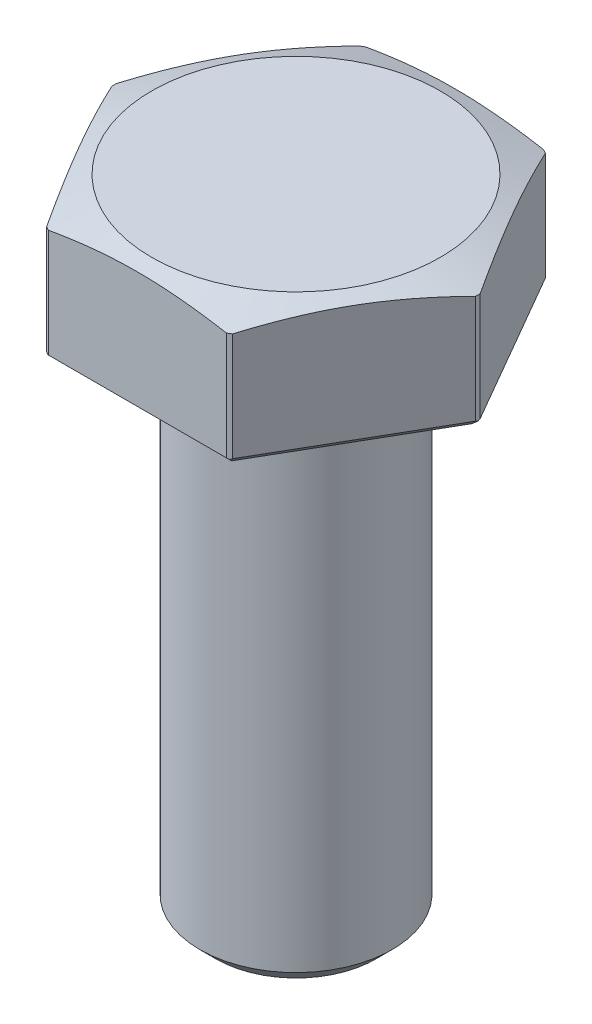
SolidWorks part; units mm, degrees
material "Chrome Stainless Steel"
ref_plane "Front" through (0, 0, 0) normal (0, 0, 1) x (1, 0, 0)
ref_plane "Top" through (0, 0, 0) normal (0, 1, 0) x (1, 0, 0)
ref_plane "Right" through (0, 0, 0) normal (1, 0, 0) x (0, 0, -1)
sketch "Sketch1" plane through (0, 0, 0) normal (1, 0, 0) x (0, 0, -1)
  line L0 (0, 15.9697) -> (0, 0) construction
  line L1 (0, 0) -> (15.0519, 0) construction
  line L2 (0, 4) -> (4.5, 4)
  line L3 (5.675, 3.5723) -> (5.675, 0)
  line L4 (5.675, 0) -> (4.75, 0)
  line L5 (4.75, 0) -> (4.4, -0.15)
  line L6 (4.4, -0.15) -> (3, -0.15)
  line L7 (2.875, -0.2) -> (2.75, -0.2)
  line L8 (2.75, -0.2) -> (2.75, -0.65)
  line L9 (2.75, -0.65) -> (3, -0.9)
  line L10 (3, -0.9) -> (3, -15.45)
  line L11 (3, -15.45) -> (2.5, -15.95)
  line L12 (2.5, -15.95) -> (0, -15.95)
  line L13 (0, -15.95) -> (0, 4)
  line L14 (4.5, 4) -> (5.675, 3.5723)
  arc A0 (3, -0.15) -> (2.875, -0.2) centre (3, -0.3313) ccw
  point P12 (2.875, -0.775)
  dimension "D1" = 4
  dimension "D2" = 0.15
  dimension "D3" = 9.5
  dimension "D4" = 8.8
  dimension "D5" = 11.35
  dimension "D6" = 15.8
  dimension "D7" = 6
  dimension "D8" = 5.5
  dimension "D9" = 45
  dimension "D10" = 0.75
  dimension "D11" = 6
  dimension "D12" = 0.2
  dimension "D13" = 0.5
  dimension "D14" = 9
  dimension "D15" = 20
revolve "Revolve1" add sketch "Sketch1" angle 360 about L0
cosmetic thread "Cosmetic Thread1" parameters "D2"=4.891
sketch "Sketch2" plane through (0, 4, 0) normal (0, 1, 0) x (1, 0, 0)
  line L1 (2.8579, -4.95) -> (5.7158, 0)
  line L2 (5.7158, 0) -> (2.8579, 4.95)
  line L3 (2.8579, 4.95) -> (-2.8579, 4.95)
  line L4 (-2.8579, 4.95) -> (-5.7158, 0)
  line L5 (-5.7158, 0) -> (-2.8579, -4.95)
  line L6 (-2.8579, -4.95) -> (2.8579, -4.95)
  circle A0 centre (0, 0) radius 4.95 construction
  dimension "D1" = 9.9
extrude "Cut-Extrude1" cut sketch "Sketch2" against normal up to next (19.95 mm away) flip side to cut
chamfer "Chamfer1" distance 0.2 angle 45 6 edges at (-4.2868, 0, 2.475) (0, 0, 4.95) (4.2868, 0, 2.475) (-4.2868, 0, -2.475) (0, 0, -4.95) (4.2868, 0, -2.475)
